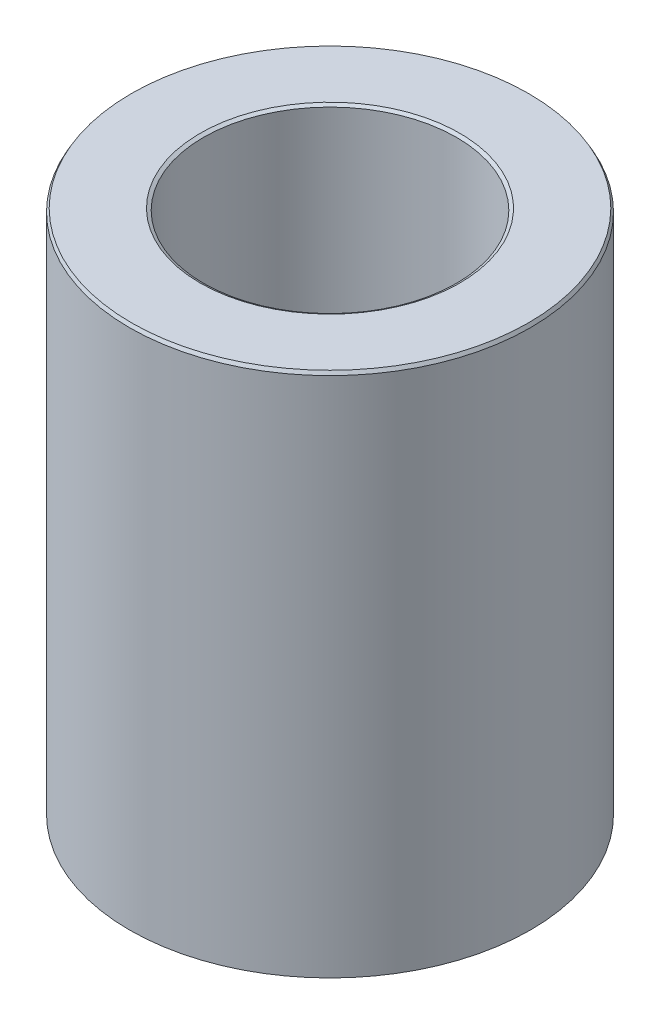
SolidWorks part; units mm, degrees
ref_plane "Front Plane" through (0, 0, 0) normal (0, 0, 1) x (1, 0, 0)
ref_plane "Top Plane" through (0, 0, 0) normal (0, 1, 0) x (1, 0, 0)
ref_plane "Right Plane" through (0, 0, 0) normal (1, 0, 0) x (0, 0, -1)
sketch "Sketch1" plane through (0, 0, 0) normal (0, 1, 0) x (1, 0, 0)
  circle A0 centre (0, 0) radius 15
  dimension "SLEEVE_OD" = 30
extrude "Boss-Extrude1" add sketch "Sketch1" along normal blind 39.4217
sketch "Sketch2" plane through (0, 0, 0) normal (0, 1, 0) x (1, 0, 0)
  circle A0 centre (0, 0) radius 9.4637
  dimension "BORE_D" = 18.9274
extrude "Cut-Extrude1" cut sketch "Sketch2" along normal through all
chamfer "Chamfer1" distance 0.2479 angle 29.683 4 edges at (0, 39.4217, 9.4637) (0, 0, 9.4637) (0, 0, 15) (0, 39.4217, 15) first distance on face at (0, 39.4217, 9.4637) first distance on face at (0, 0, 9.4637) first distance on face at (0, 39.4217, 15)
